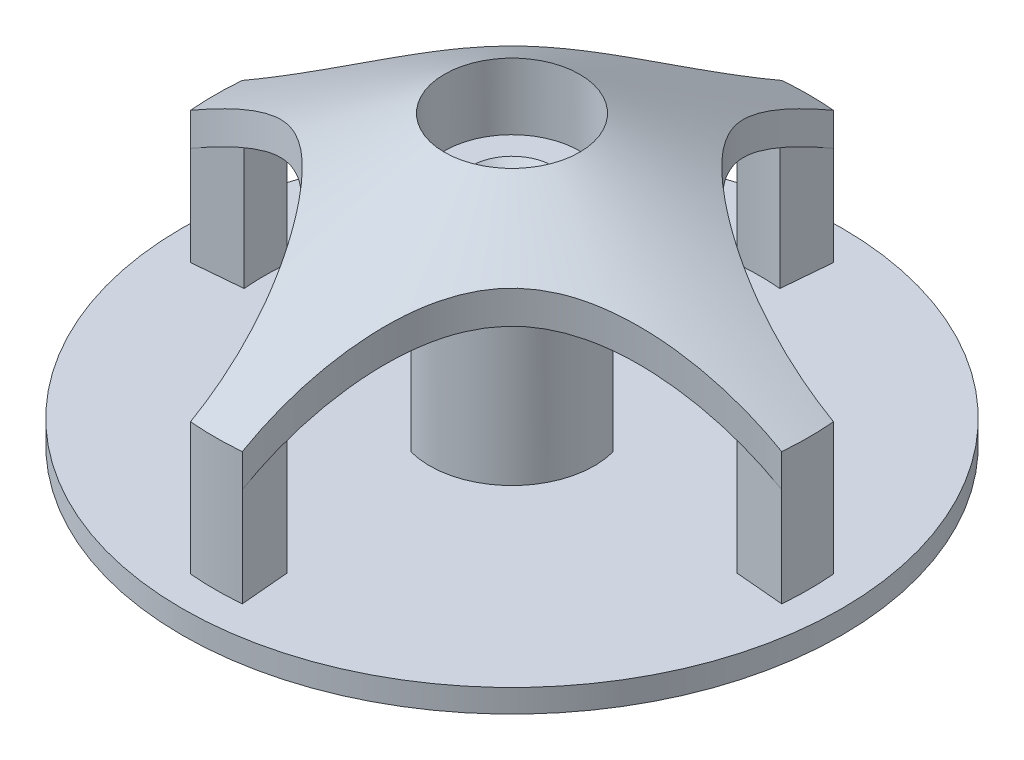
SolidWorks part; units mm, degrees
ref_plane "Front Plane" through (0, 0, 0) normal (0, 0, 1) x (1, 0, 0)
ref_plane "Top Plane" through (0, 0, 0) normal (0, 1, 0) x (1, 0, 0)
ref_plane "Right Plane" through (0, 0, 0) normal (1, 0, 0) x (0, 0, -1)
sketch "Sketch1" plane through (0, 0, 0) normal (0, 1, 0) x (1, 0, 0)
  circle A0 centre (0, 0) radius 127
  dimension "D1" = 254
extrude "Base of base" add sketch "Sketch1" along normal blind 8.89
ref_plane "Top Platform Offset" through (0, 46.99, 0) normal (0, 1, 0) x (1, 0, 0)
sketch "Sketch15" plane through (0, 0, 0) normal (1, 0, 0) x (0, 0, -1)
  line L0 (0, 8.89) -> (0, 44.378) construction
  line L2 (127, 8.89) -> (-127, 8.89) construction
sketch "Sketch7" plane through (0, 0, 0) normal (1, 0, 0) x (0, 0, -1)
  line L1 (127, 8.89) -> (-127, 8.89)
  line L2 (-114.3, 46.99) -> (0, 46.99) construction
  line L3 (-114.3, 46.99) -> (0, 112.9811)
  line L4 (-114.3, 46.99) -> (-114.3, 59.69)
  line L5 (-114.3, 59.69) -> (0, 125.6811)
  line L6 (0, 125.6811) -> (0, 112.9811)
  point P2 (0, 0)
  point P7 (0, 0)
  point P8 (0, 8.89)
  dimension "D1" = 30
  dimension "D2" = 114.3
  dimension "D3" = 38.1
revolve "Top Part of Base" add sketch "Sketch7" angle 360 about L0 region at (0, 86.3356, 57.15)
ref_plane "Offset Plane for Cuts" through (0, 125.6811, 0) normal (0, 1, 0) x (1, 0, 0)
sketch "Sketch8" plane through (0, 125.6811, 0) normal (0, 1, 0) x (1, 0, 0)
  circle A0 centre (0, 0) radius 26.035
  dimension "D1" = 52.07
extrude "Ball Bearing Cut" cut sketch "Sketch8" against normal up to surface (27.7313 mm away)
sketch "Sketch10" plane through (0, 8.89, 0) normal (0, 1, 0) x (1, 0, 0)
  line L0 (0, 0) -> (0, 114.3) construction
  line L1 (0, 0) -> (9.9619, 113.8651)
  line L2 (0, 0) -> (-9.9619, 113.8651)
  circle A0 centre (0, 0) radius 114.3 construction
  circle A1 centre (0, 0) radius 114.3
  circle A2 centre (0, 0) radius 95.25
  arc A3 (9.9619, 113.8651) -> (-9.9619, 113.8651) centre (0, 0) ccw
  dimension "D1" = 190.5
  dimension "D2" = 5
extrude "Support" add sketch "Sketch10" along normal up to surface (49.0985 mm away) contours A2 L0 A3 L2 | L0 A2 L1 A1 region at (-4.5814, 8.89, -104.9303) region at (4.5814, 8.89, -104.9303) up to face at (0, 97.9498, -26.035)
pattern_circular "Supports" count 4 every 90 about axis through (0, 8.89, 0) along (0, 1, 0) of "Support"
sketch "Sketch12" plane through (0, 125.6811, 0) normal (0, 1, 0) x (1, 0, 0)
  arc A4 (9.9619, 113.8651) -> (113.8651, 9.9619) centre (113.8651, 113.8651) ccw
  arc A9 (-9.9619, 113.8651) -> (-113.8651, 9.9619) centre (-113.8651, 113.8651) cw
  arc A10 (-113.8651, -9.9619) -> (-9.9619, -113.8651) centre (-113.8651, -113.8651) cw
  arc A11 (9.9619, -113.8651) -> (113.8651, -9.9619) centre (113.8651, -113.8651) cw
  arc A12 (-113.8651, -9.9619) -> (-9.9619, -113.8651) centre (0, 0) ccw
  arc A13 (113.8651, 9.9619) -> (9.9619, 113.8651) centre (0, 0) ccw
  arc A14 (-9.9619, 113.8651) -> (-113.8651, 9.9619) centre (0, 0) ccw
  arc A15 (9.9619, -113.8651) -> (113.8651, -9.9619) centre (0, 0) ccw
extrude "Cut for Printabiity" cut sketch "Sketch12" against normal up to surface (78.6911 mm away) contours A10 A12 | A9 A14 | A4 A13 | A11 A15 region at (60.8149, 125.6811, -60.8149) region at (-60.8149, 125.6811, -60.8149) region at (-60.8149, 125.6811, 60.8149) region at (60.8149, 125.6811, 60.8149) up to face at (0, 52.4893, 0)
sketch "Reference for height of base" plane through (0, 0, 0) normal (0, 0, 1) x (1, 0, 0)
  line L0 (-26.035, 97.9498) -> (26.035, 97.9498) construction
  line L1 (-26.035, 97.9498) -> (26.035, 97.9498)
  line L2 (26.035, 97.9498) -> (26.035, 8.89) construction
  line L3 (127, 8.89) -> (-127, 8.89) construction
  dimension "D1" = 89.0598
sketch "Sketch14" plane through (0, 8.89, 0) normal (0, 1, 0) x (1, 0, 0)
  circle A1 centre (0, 0) radius 13.335
  circle A2 centre (0, 0) radius 26.035 construction
  circle A3 centre (0, 0) radius 26.035
  circle A4 centre (0, 0) radius 31.75
  dimension "D1" = 26.67
  dimension "D3" = 63.5
extrude "Holder for Shoulder" add sketch "Sketch14" along normal blind 76.2 contours A3 A1 region at (-25.2986, 8.89, 0)
extrude "Center Cylinder" add sketch "Sketch14<3>" along normal up to surface (85.7603 mm away) contours A4 A3 region at (-30.852, 8.89, 0) up to face at (0, 97.9498, -26.035)
sketch "Sketch14<3>" plane through (0, 8.89, 0) normal (0, 1, 0) x (1, 0, 0) same geometry as "Sketch14"
chamfer "Funnel into Snap in Place" distance 2.54 angle 45 1 edges at (0, 85.09, 13.335)
ref_plane "Plane for Accessibility Cut" through (-61.9135, 0, 61.9135) normal (0.7071, 0, -0.7071) x (-0.7071, 0, -0.7071)
sketch "Sketch19" plane through (-61.9135, 0, 61.9135) normal (0.7071, 0, -0.7071) x (-0.7071, 0, -0.7071)
  line L0 (31.75, 8.89) -> (-31.75, 8.89) construction
  line L1 (31.75, 8.89) -> (-31.75, 8.89)
  line L2 (0, 8.89) -> (0, 44.378) construction
  line L3 (15.875, 8.89) -> (-15.875, 8.89)
  line L4 (15.875, 8.89) -> (15.875, 59.69)
  line L5 (15.875, 59.69) -> (-15.875, 59.69)
  line L6 (-15.875, 8.89) -> (-15.875, 59.69)
  line L7 (0, 8.89) -> (0, 44.378)
  line L8 (0, 59.69) -> (-15.875, 43.815)
  line L9 (0, 59.69) -> (15.875, 43.815)
  dimension "D1" = 31.75
  dimension "D2" = 15.875
  dimension "D3" = 15.875
  dimension "D4" = 50.8
  dimension "D5" = 45
  dimension "D6" = 45
extrude "Accessibility Cut" cut sketch "Sketch19" along normal through all contours L9 L8 L6 L3 L1 L4 region at (-67.5261, 9.4891, 56.3008)
sketch "Sketch20" plane through (0, 0, 0) normal (1, 0, 0) x (0, 0, -1)
  line L0 (-13.335, 82.55) -> (13.335, 82.55) construction
  line L1 (-13.335, 82.55) -> (13.335, 82.55)
  line L2 (13.335, 82.55) -> (13.335, 88.2939) construction
  line L3 (13.335, 79.375) -> (15.875, 79.375)
  line L4 (15.875, 79.375) -> (13.335, 74.295)
  line L5 (13.335, 74.295) -> (13.335, 79.375)
  dimension "D1" = 3.175
  dimension "D2" = 5.08
  dimension "D3" = 2.54
revolve "Cut-Revolve1" cut sketch "Sketch20" angle 360 about L0 region at (0, 77.6817, -14.1817)
